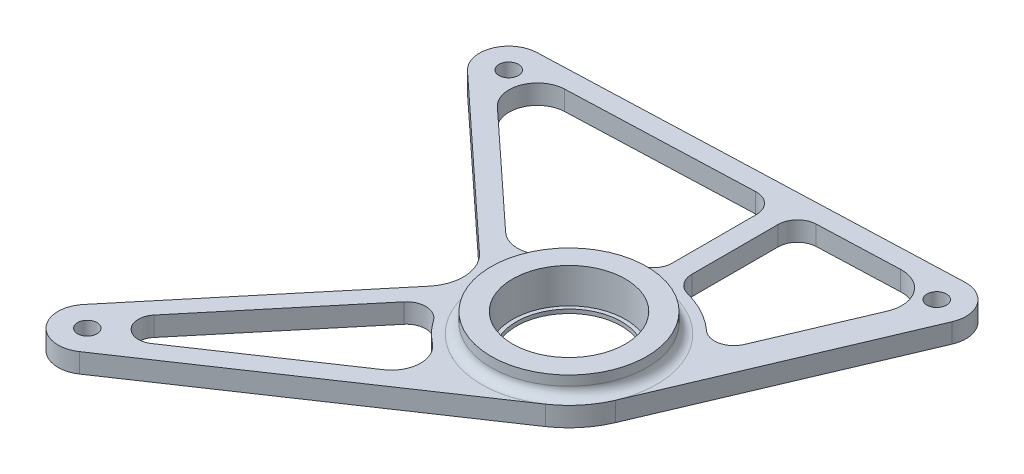
SolidWorks part; units mm, degrees
material "7050-T73510"
ref_plane "Płaszczyzna przednia" through (0, 0, 0) normal (0, 0, 1) x (1, 0, 0)
ref_plane "Płaszczyzna górna" through (0, 0, 0) normal (0, 1, 0) x (1, 0, 0)
ref_plane "Płaszczyzna prawa" through (0, 0, 0) normal (1, 0, 0) x (0, 0, -1)
sketch "Szkic1" plane through (0, 0, 0) normal (0, 1, 0) x (1, 0, 0)
  line L1 (-1703.3489, -133.2209) -> (-1915.5489, -140.9908)
  line L3 (-1740.5781, -275.5848) -> (-1688.9927, -154.0725)
  line L5 (-1756.869, -295.3287) -> (-1899.9755, -391.673)
  line L7 (-1827, -258) -> (-1925.1969, -166.9819)
  line L9 (-1919.8833, -369.6363) -> (-1827, -258)
  line L10 (-1685.3, -117.9) -> (-1702.8, -148.2109) construction
  line L11 (-1956.7028, -117.9) -> (-1413.8972, -117.9) construction
  line L12 (-55, 0) -> (55, 0) construction
  line L13 (-2095.3204, -130) -> (-1764.6796, -130) construction
  line L14 (-1930, -130) -> (-1915, -155.9808) construction
  circle A1 centre (-1930, -130) radius 12.5
  circle A2 centre (-1685.3, -117.9) radius 12.5
  arc A3 (-1740.5781, -275.5848) -> (-1756.869, -295.3287) centre (-1782, -258) cw
  arc A4 (-1688.9927, -154.0725) -> (-1703.3489, -133.2209) centre (-1702.8, -148.2109) ccw
  arc A5 (-1925.1969, -166.9819) -> (-1915.5489, -140.9908) centre (-1915, -155.9808) cw
  circle A6 centre (-1930, -400) radius 12.5
  arc A7 (-1899.9755, -391.673) -> (-1919.8833, -369.6363) centre (-1908.3525, -379.2301) cw
  point P22 (-1685.3, -117.9)
  point P33 (-1930, -130)
  dimension "D4" = 25
  dimension "D5" = 25
  dimension "D10" = 45
  dimension "D11" = 15
  dimension "D12" = 15
  dimension "D13" = 25
  dimension "D15" = 15
  dimension "D17" = 1685.3
  dimension "D16" = 45
  dimension "D3" = 1930
  dimension "D7" = 130
  dimension "D9" = 35
  dimension "D6" = 258
  dimension "D8" = 1930
  dimension "D14" = 270
  dimension "D18" = 60
  dimension "D19" = 1782
  dimension "D20" = 126.3525
  dimension "D21" = 60
  dimension "D22" = 30
  dimension "D23" = 30
  dimension "D24" = 117.9
extrude "Dodanie-wyciągnięcie1" add sketch "Szkic1" along normal blind 10
hole_wizard "Otwór1" positions "Szkic2" profile "Szkic3" legacy
sketch "Szkic2" plane through (0, 10, 0) normal (0, 1, 0) x (1, 0, 0)
  arc A0 (-1756.869, -295.3287) -> (-1740.5781, -275.5848) centre (-1782, -258) ccw construction
  point P0 (-1782, -258)
sketch "Szkic3" plane through (-1782, 10, 258) normal (1, 0, 0) x (0, 0, 1)
  line L0 (0, 0) -> (0, 8)
  line L1 (0, 8) -> (29, 8)
  line L2 (29, 8) -> (29, 0)
  line L3 (29, 0) -> (0, 0)
  line L4 (0, 110) -> (0, -10) construction
  dimension "Średnica" = 58
  dimension "Głębokość" = 8
hole_wizard "Otwór2" positions "Szkic6" profile "Szkic7" legacy
sketch "Szkic6" plane through (0, 2, 0) normal (0, 1, 0) x (1, 0, 0)
  circle A0 centre (-1782, -258) radius 29 construction
  point P0 (-1782, -258)
sketch "Szkic7" plane through (-1782, 2, 258) normal (1, 0, 0) x (0, 0, 1)
  line L0 (0, 0) -> (0, 10)
  line L1 (0, 10) -> (27, 10)
  line L2 (27, 10) -> (27, 0)
  line L3 (27, 0) -> (0, 0)
  line L4 (0, 110) -> (0, -10) construction
  dimension "Średnica" = 54
  dimension "Głębokość" = 10
sketch "Szkic8" plane through (0, 10, 0) normal (0, 1, 0) x (1, 0, 0)
  circle A0 centre (-1782, -258) radius 29
  circle A1 centre (-1782, -258) radius 29 construction
  circle A2 centre (-1782, -258) radius 40
  dimension "D1" = 80
extrude "Dodanie-wyciągnięcie2" add sketch "Szkic8" along normal blind 10
hole_wizard "Otwór3" positions "Szkic11" profile "Szkic12" legacy
sketch "Szkic11" plane through (0, 10, 0) normal (0, 1, 0) x (1, 0, 0)
  arc A0 (-1688.9927, -154.0725) -> (-1703.3489, -133.2209) centre (-1702.8, -148.2109) ccw construction
  point P0 (-1702.8, -148.2109)
sketch "Szkic12" plane through (-1702.8, 10, 148.2109) normal (1, 0, 0) x (0, 0, 1)
  line L0 (0, 0) -> (0, 100)
  line L1 (0, 100) -> (5, 100)
  line L2 (5, 100) -> (5, 0)
  line L3 (5, 0) -> (0, 0)
  line L4 (0, 110) -> (0, -10) construction
  dimension "Średnica" = 10
  dimension "Głębokość" = 100
hole_wizard "Otwór4" positions "Szkic13" profile "Szkic14" legacy
sketch "Szkic13" plane through (0, 10, 0) normal (0, 1, 0) x (1, 0, 0)
  arc A0 (-1915.5489, -140.9908) -> (-1925.1969, -166.9819) centre (-1915, -155.9808) ccw construction
  point P0 (-1915, -155.9808)
sketch "Szkic14" plane through (-1915, 10, 155.9808) normal (1, 0, 0) x (0, 0, 1)
  line L0 (0, 0) -> (0, 100)
  line L1 (0, 100) -> (5, 100)
  line L2 (5, 100) -> (5, 0)
  line L3 (5, 0) -> (0, 0)
  line L4 (0, 110) -> (0, -10) construction
  dimension "Średnica" = 10
  dimension "Głębokość" = 100
hole_wizard "Otwór6" positions "Szkic17" profile "Szkic18" legacy end condition up to next
sketch "Szkic17" plane through (0, 10, 0) normal (0, 1, 0) x (1, 0, 0)
  arc A0 (-1919.8833, -369.6363) -> (-1899.9755, -391.673) centre (-1908.3525, -379.2301) ccw construction
  point P0 (-1908.3525, -379.2301)
sketch "Szkic18" plane through (-1908.3525, 10, 379.2301) normal (1, 0, 0) x (0, 0, 1)
  line L0 (0, 0) -> (0, 10)
  line L1 (0, 10) -> (5, 10)
  line L2 (5, 10) -> (5, 0)
  line L3 (5, 0) -> (0, 0)
  line L4 (0, 110) -> (0, -10) construction
  dimension "Średnica" = 10
  dimension "Głębokość" = 10
fillet "Zaokrąglenie7" radius 5 1 edges at (-1782, 10, 298)
sketch "Szkic19" plane through (0, 10, 0) normal (0, 1, 0) x (1, 0, 0)
  line L1 (-1892.0951, -150.1387) -> (-1787, -146.2906)
  line L2 (-1787, -146.2906) -> (-1787, -208.2506)
  line L3 (-1792.0737, -306.9747) -> (-1885.097, -369.6012)
  line L4 (-1703.3489, -133.2209) -> (-1915.5489, -140.9908) construction
  line L5 (-1829.4138, -242.1277) -> (-1901.4548, -175.3532)
  line L6 (-1827, -258) -> (-1925.1969, -166.9819) construction
  line L7 (-1710.3646, -166.0298) -> (-1738.7545, -232.9037)
  line L8 (-1777, -208.2506) -> (-1777, -145.9244)
  line L9 (-1777, -145.9244) -> (-1725.5053, -144.0389)
  line L10 (-1740.5781, -275.5848) -> (-1688.9927, -154.0725) construction
  line L11 (-1897.1181, -356.2946) -> (-1838.7498, -286.1419)
  line L12 (-1756.869, -295.3287) -> (-1899.9755, -391.673) construction
  line L13 (-1919.8833, -369.6363) -> (-1827, -258) construction
  arc A0 (-1829.4138, -242.1277) -> (-1787, -208.2506) centre (-1782, -258) cw
  circle A1 centre (-1782, -258) radius 40 construction
  arc A2 (-1901.4548, -175.3532) -> (-1892.0951, -150.1387) centre (-1891.5627, -164.6808) cw
  arc A3 (-1885.097, -369.6012) -> (-1897.1181, -356.2946) centre (-1890.1554, -362.0877) cw
  arc A4 (-1738.7545, -232.9037) -> (-1777, -208.2506) centre (-1782, -258) ccw
  arc A5 (-1725.5053, -144.0389) -> (-1710.3646, -166.0298) centre (-1724.9264, -159.848) cw
  circle A6 centre (-1702.8, -148.2109) radius 5 construction
  circle A7 centre (-1915, -155.9808) radius 5 construction
  circle A8 centre (-1908.3525, -379.2301) radius 5 construction
  arc A10 (-1792.0737, -306.9747) -> (-1822.8856, -286.7814) centre (-1782, -258) cw
  arc A11 (-1822.8856, -286.7814) -> (-1838.7498, -286.1419) centre (-1831.0627, -292.5377) ccw
  dimension "D3" = 25
  dimension "D4" = 50
  dimension "D8" = 50
  dimension "D14" = 50
  dimension "D15" = 10
  dimension "D2" = 10
  dimension "15" = 10
  dimension "D5" = 10
  dimension "D6" = 15
  dimension "D7" = 25
  dimension "D9" = 10
  dimension "D10" = 5
  dimension "D11" = 10
  dimension "D13" = 25
extrude "Wytnij-wyciągnięcie1" cut sketch "Szkic19" against normal through all
fillet "Zaokrąglenie8" radius 10 5 edges at (-1738.7545, 5, 232.9037) (-1777, 5, 208.2506) (-1787, 5, 208.2506) (-1787, 5, 146.2906) (-1777, 5, 145.9244)
fillet "Zaokrąglenie9" radius 15 2 edges at (-1829.4138, 5, 242.1277) (-1792.0737, 5, 306.9747)
fillet "Zaokrąglenie10" radius 20 1 edges at (-1827, 5, 258)
